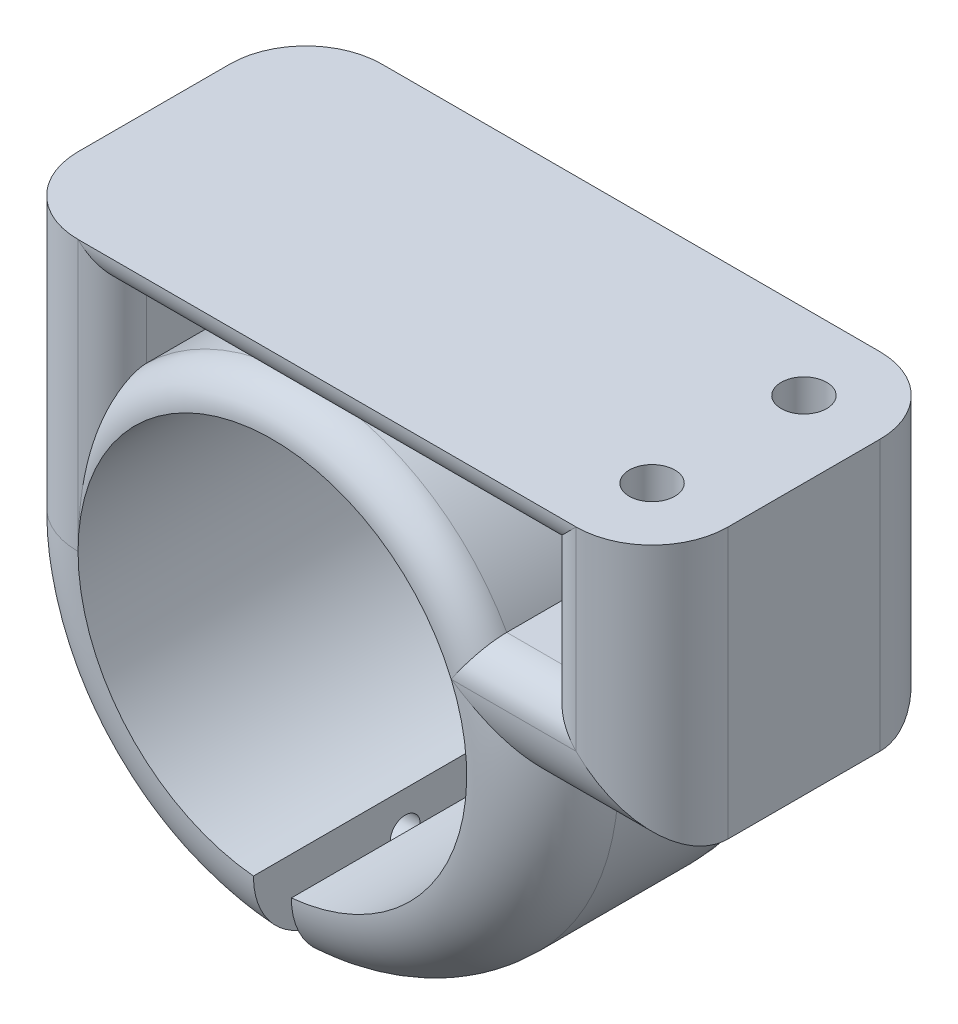
SolidWorks part; units mm, degrees
material "ABS"
ref_plane "Front Plane" through (0, 0, 0) normal (0, 0, 1) x (1, 0, 0)
ref_plane "Top Plane" through (0, 0, 0) normal (0, 1, 0) x (1, 0, 0)
ref_plane "Right Plane" through (0, 0, 0) normal (1, 0, 0) x (0, 0, -1)
sketch "Sketch2" plane through (0, 0, 0) normal (0, 1, 0) x (1, 0, 0)
  line L0 (-31.75, -12.7) -> (-31.75, 12.7) construction
  line L1 (44.45, 25.4) -> (-44.45, 25.4)
  line L2 (44.45, 25.4) -> (44.45, -25.4)
  line L3 (44.45, -25.4) -> (-44.45, -25.4)
  line L4 (-44.45, 25.4) -> (-44.45, -25.4)
  line L5 (44.45, 25.4) -> (-44.45, -25.4) construction
  line L6 (44.45, -25.4) -> (-44.45, 25.4) construction
  line L7 (-31.75, 0) -> (0, 0) construction
  line L8 (-19.05, 25.4) -> (-19.05, -25.4)
  circle A0 centre (-31.75, 12.7) radius 3.81
  circle A1 centre (-31.75, -12.7) radius 3.81
  point P0 (0, 0)
  point P1 (0, 0)
  point P7 (115.9564, 68.2319)
  dimension "D5" = 7.62
  dimension "D1" = 88.9
  dimension "D2" = 50.8
  dimension "D3" = 12.7
  dimension "D4" = 25.4
  dimension "D6" = 12.7
extrude "Boss-Extrude1" add sketch "Sketch2" against normal blind 25.4 contours L8 L1 L4 L3 A1 A0 region at (-31.75, 0, 0)
sketch "Sketch3" plane through (0, 0, 0) normal (0, 0, 1) x (1, 0, 0)
  line L0 (-31.75, 0) -> (-31.75, -12.7) construction
  line L1 (-19.05, 0) -> (-44.45, 0) construction
  line L2 (-31.75, -12.7) -> (-82.55, -12.7) construction
  line L3 (-82.55, -12.7) -> (-82.55, -45.2) construction
  line L4 (-44.45, -25.4) -> (-44.45, 0) construction
  line L5 (-44.45, 0) -> (-127.75, 0)
  line L6 (-127.75, 0) -> (-127.75, -45.2)
  line L7 (-127.75, -45.2) -> (-115.05, -45.2)
  line L8 (-19.05, -25.4) -> (-19.05, -45.2)
  line L9 (-19.05, -45.2) -> (-50.05, -45.2)
  line L10 (-19.05, -25.4) -> (-44.45, -25.4) construction
  line L11 (-44.45, -25.4) -> (-44.45, 0)
  line L12 (-19.05, -25.4) -> (-44.45, -25.4)
  circle A0 centre (-82.55, -45.2) radius 32.5
  arc A1 (-127.75, -45.2) -> (-37.35, -45.2) centre (-82.55, -45.2) ccw
  dimension "D1" = 65
  dimension "D2" = 32.5
  dimension "D3" = 12.7
  dimension "D4" = 38.1
  dimension "D5" = 12.7
extrude "Boss-Extrude2" add sketch "Sketch3" along normal mid plane 50.8 contours A0 L9 L8 L12 L11 L5 L6 L7 | L7 A1 L9 A0 region at (-45.6272, -12.7, 0) region at (-121.4, -46.2107, 0)
sketch "Sketch4" plane through (0, 0, 25.4) normal (0, 0, 1) x (1, 0, 0)
  line L0 (-82.55, -45.2) -> (-82.55, -77.7) construction
  line L2 (-85.725, -104.5667) -> (-79.375, -104.5667)
  line L3 (-85.725, -104.5667) -> (-85.725, -50.8333)
  line L4 (-85.725, -50.8333) -> (-79.375, -50.8333)
  line L5 (-79.375, -104.5667) -> (-79.375, -50.8333)
  line L6 (-85.725, -104.5667) -> (-79.375, -50.8333) construction
  line L7 (-85.725, -50.8333) -> (-79.375, -104.5667) construction
  circle A0 centre (-82.55, -45.2) radius 32.5 construction
  circle A1 centre (-82.55, -45.2) radius 32.5
  arc M4 (-127.75, -45.2) -> (-37.35, -45.2) centre (-82.55, -45.2) ccw
  circle M7 centre (-82.55, -45.2) radius 32.5
  dimension "D1" = 6.35
extrude "Cut-Extrude1" cut sketch "Sketch4" against normal blind 170.18 contours L2 L5 L3 M4 | L5 L4 L3 M7 | L5 L3 M4 M7 region at (-82.55, -97.4647, 25.4) region at (-82.55, -84.0055, 25.4) region at (-82.55, -64.2408, 25.4)
sketch "Sketch5" plane through (-127.75, 0, 0) normal (-1, 0, 0) x (0, 0, 1)
  line L0 (25.4, -77.5445) -> (-25.4, -77.5445) construction
  line L1 (25.4, -77.5445) -> (-25.4, -77.5445)
  line L2 (25.4, -77.5445) -> (25.4, -90.2884)
  line L3 (25.4, -90.2884) -> (-25.4, -90.2884) construction
  line L4 (25.4, -90.2884) -> (-25.4, -90.2884)
  line L5 (-25.4, -77.5445) -> (-25.4, -90.2884)
  line L6 (0, -90.2884) -> (0, -77.5445) construction
  line L8 (-9.525, -88.0439) -> (9.525, -88.0439)
  line L9 (-9.525, -88.0439) -> (-9.525, -79.7889)
  line L10 (-9.525, -79.7889) -> (9.525, -79.7889)
  line L11 (9.525, -88.0439) -> (9.525, -79.7889)
  line L12 (-9.525, -88.0439) -> (9.525, -79.7889) construction
  line L13 (-9.525, -79.7889) -> (9.525, -88.0439) construction
  circle A0 centre (0, -83.9164) radius 2.5
  dimension "D1" = 5
  dimension "D2" = 19.05
  dimension "D3" = 8.255
extrude "Cut-Extrude2" cut sketch "Sketch5" against normal blind 170.18 contours L6 A0 | A0 L6 region at (-127.75, -83.9164, 1.061) region at (-127.75, -83.9164, -1.061)
extrude "Cut-Extrude3" cut sketch "Sketch5<3>" against normal blind 32.004 contours L8 L11 L10 L9 A0 region at (-127.75, -83.9164, -9.3174)
sketch "Sketch5<3>" plane through (-127.75, 0, 0) normal (-1, 0, 0) x (0, 0, 1) same geometry as "Sketch5"
ref_plane "Plane1" through (-82.55, 0, 0) normal (-1, 0, 0) x (0, 0, 1)
mirror "Mirror1" about plane through (-82.55, 0, 0) normal (-1, 0, 0) of "Cut-Extrude3"
sketch "Sketch6" plane through (0, -25.4, 0) normal (0, 1, 0) x (1, 0, 0)
  circle A0 centre (-31.75, -12.7) radius 3.81 construction
  circle A1 centre (-31.75, 12.7) radius 3.81 construction
  circle A2 centre (-31.75, -12.7) radius 3.81
  circle A3 centre (-31.75, 12.7) radius 3.81
extrude "Cut-Extrude4" cut sketch "Sketch6" against normal blind 32.004
fillet "Fillet1" radius 12.7 10 edges at (-115.6147, -76.0183, 25.4) (-19.05, -22.6, 25.4) (-28.2, -45.2, 25.4) (-49.4853, -76.0183, 25.4) (-127.75, -22.6, 25.4) (-127.75, -22.6, -25.4) (-115.6147, -76.0183, -25.4) (-49.4853, -76.0183, -25.4) (-28.2, -45.2, -25.4) (-19.05, -22.6, -25.4)
sketch "Sketch7" plane through (0, 0, 25.4) normal (0, 0, 1) x (1, 0, 0)
  line L4 (-49.0646, -26.785) -> (-37.465, -26.785)
  line L5 (-49.0646, -26.785) -> (-37.465, -26.785)
  line L6 (-37.465, -26.785) -> (-37.465, -5.715)
  line L7 (-37.465, -26.785) -> (-37.465, -5.715)
  line L8 (-82.55, -45.2) -> (-82.55, -5.715) construction
  line L9 (-95.25, -5.715) -> (-69.85, -5.715)
  line L14 (-37.465, -5.715) -> (-109.335, -5.715)
  line L15 (-109.335, -5.715) -> (-109.335, -17.9429)
  line L18 (-37.465, -5.715) -> (-109.335, -5.715)
  line L19 (-109.335, -5.715) -> (-109.335, -17.9429)
  arc A3 (-49.0646, -26.785) -> (-109.335, -17.9429) centre (-82.55, -45.2) ccw
  arc A4 (-49.0646, -26.785) -> (-109.335, -17.9429) centre (-82.55, -45.2) ccw
  point P3 (-82.55, -5.715)
  dimension "D1" = 5.715
extrude "Cut-Extrude6" cut sketch "Sketch7" against normal up to surface (50.8 mm away) contours A4 L18 L19 | A4 L5 L7 L18 region at (-61.1784, -12.892, 25.4) up to face at (-70.2844, -16.9405, -25.4)
fillet "Fillet2" radius 5.715 10 edges at (-43.2648, -26.785, 25.4) (-37.465, -16.25, 25.4) (-73.4, -5.715, 25.4) (-109.335, -11.8289, 25.4) (-77.003, -7.3897, 25.4) (-109.335, -11.8289, -25.4) (-73.4, -5.715, -25.4) (-37.465, -16.25, -25.4) (-43.2648, -26.785, -25.4) (-77.003, -7.3897, -25.4)
